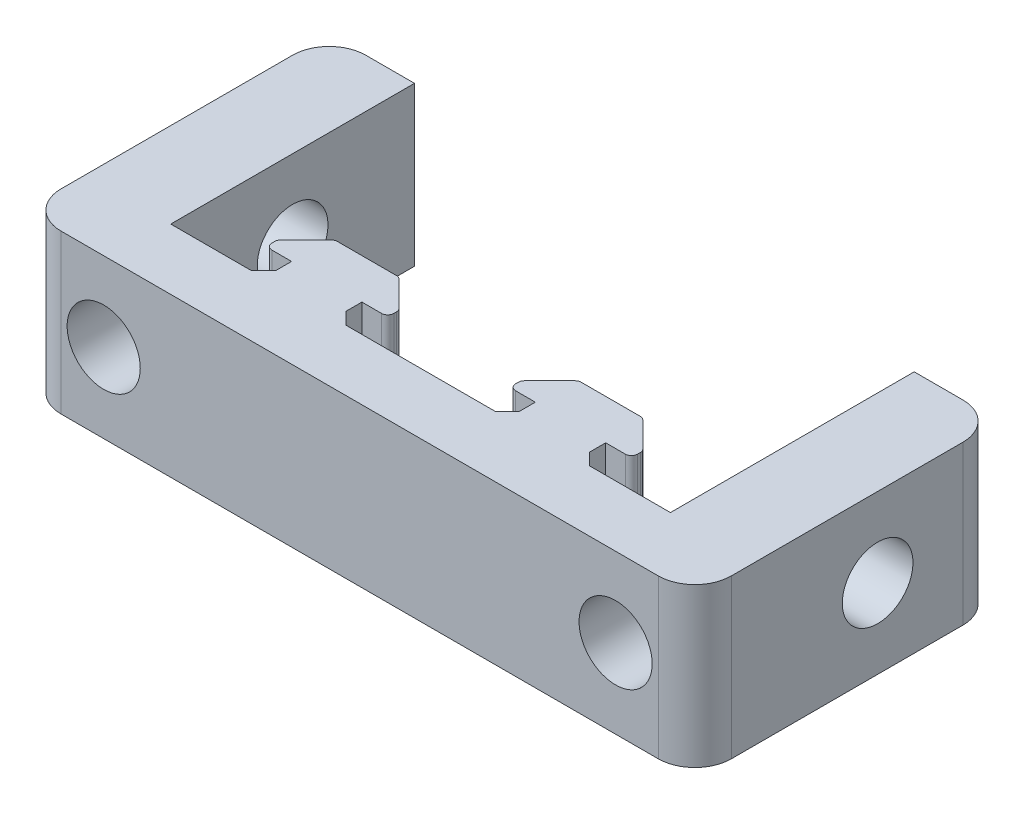
SolidWorks part; units mm, degrees
ref_plane "Front Plane" through (0, 0, 0) normal (0, 0, 1) x (1, 0, 0)
ref_plane "Top Plane" through (0, 0, 0) normal (0, 1, 0) x (1, 0, 0)
ref_plane "Right Plane" through (0, 0, 0) normal (1, 0, 0) x (0, 0, -1)
sketch "Sketch1" plane through (0, 0, 0) normal (0, 0, 1) x (1, 0, 0)
  line L5 (-27.5, -6.5) -> (27.5, -6.5)
  line L6 (-27.5, -6.5) -> (-27.5, 6.5)
  line L7 (-27.5, 6.5) -> (27.5, 6.5)
  line L8 (27.5, -6.5) -> (27.5, 6.5)
  line L9 (-27.5, -6.5) -> (27.5, 6.5) construction
  line L10 (-27.5, 6.5) -> (27.5, -6.5) construction
  point P0 (0, 0)
  dimension "D1" = 13
  dimension "D2" = 55
extrude "Boss-Extrude1" add sketch "Sketch1" along normal blind 10
sketch "Sketch2" plane through (0, 0, 10) normal (0, 0, 1) x (1, 0, 0)
  line L0 (27.5, -6.5) -> (27.5, 6.5) construction
  line L1 (-27.5, -6.5) -> (27.5, -6.5)
  line L2 (-27.5, -6.5) -> (-27.5, 6.5)
  line L3 (-27.5, 6.5) -> (27.5, 6.5)
  line L4 (27.5, -6.5) -> (27.5, 6.5)
  line L5 (-27.5, -6.5) -> (27.5, 6.5) construction
  line L6 (-27.5, 6.5) -> (27.5, -6.5) construction
  line L7 (-27.5, -6.5) -> (27.5, -6.5) construction
  point P0 (0, 0)
extrude "Cut-Extrude1" cut sketch "Sketch2" against normal offset from surface (5 mm away) 5 contours L3 L4 L1 L2 up to face at (0, 0, 0)
sketch "Sketch4" plane through (0, 0, 5) normal (0, 0, 1) x (1, 0, 0)
  line L0 (21, 0) -> (-21, 0) construction
  circle A0 centre (21, 0) radius 3
  circle A1 centre (-21, 0) radius 3
  point P4 (0, 0)
  dimension "D2" = 6
  dimension "D1" = 42
extrude "Cut-Extrude2" cut sketch "Sketch4" against normal up to next
sketch "Sketch5" plane through (0, 6.5, 0) normal (0, 1, 0) x (1, 0, 0)
  line L1 (9.9, 5.5995) -> (12.6324, 5.5995)
  line L2 (12.6324, 5.5995) -> (15, 3.2319)
  line L3 (15, 3.2319) -> (15, 2.3)
  line L4 (15, 2.3) -> (12.8865, 2.3)
  line L5 (12.8865, 2.3) -> (12.8865, 0.9829)
  line L6 (12.8865, 0.9829) -> (13.8694, 0)
  line L7 (6.1306, 0) -> (7.1135, 0.9829)
  line L8 (7.1135, 0.9829) -> (7.1135, 2.3)
  line L9 (7.1135, 2.3) -> (5, 2.3)
  line L10 (5, 2.3) -> (5, 3.2319)
  line L11 (5, 3.2319) -> (7.3676, 5.5995)
  line L12 (7.3676, 5.5995) -> (9.9, 5.5995)
  line L14 (10.1, 5.5995) -> (12.6324, 5.5995) construction
  line L17 (13.8694, 0) -> (6.1306, 0)
  line L18 (12.8865, 0.9829) -> (14.0205, -0.1511) construction
  line L19 (5.9795, -0.1511) -> (7.1135, 0.9829) construction
  line L313 (0, 1.8) -> (0, 0)
  line L314 (0, 0) -> (5.1372, 0)
  line L315 (5.6259, 0.2024) -> (6.6135, 1.19)
  line L316 (6.6135, 1.19) -> (6.6135, 1.8)
  line L317 (6.6135, 1.8) -> (4.5, 1.8)
  line L318 (4.5, 1.8) -> (4.5, 3.439)
  line L319 (4.5, 3.439) -> (7.1605, 6.0995)
  line L320 (7.1605, 6.0995) -> (9.9, 6.0995)
  line L321 (9.9, 6.0995) -> (10, 6.1995)
  line L322 (10, 6.1995) -> (10.1, 6.0995)
  line L323 (10.1, 6.0995) -> (12.8395, 6.0995)
  line L324 (12.8395, 6.0995) -> (15.5, 3.439)
  line L325 (15.5, 3.439) -> (15.5, 1.8)
  line L326 (15.5, 1.8) -> (13.3865, 1.8)
  line L327 (13.3865, 1.8) -> (13.3865, 1.19)
  line L328 (13.3865, 1.19) -> (14.3741, 0.2024)
  line L329 (14.8628, 0) -> (18.5, 0)
  line L330 (20, 1.5) -> (20, 5.1372)
  line L331 (19.7976, 5.6259) -> (18.81, 6.6135)
  line L332 (18.81, 6.6135) -> (18.2, 6.6135)
  line L333 (18.2, 6.6135) -> (18.2, 4.5)
  line L334 (18.2, 4.5) -> (16.561, 4.5)
  line L335 (16.561, 4.5) -> (13.9005, 7.1605)
  line L336 (13.9005, 7.1605) -> (13.9005, 9.9)
  line L337 (13.9005, 9.9) -> (13.8005, 10)
  line L338 (13.8005, 10) -> (13.9005, 10.1)
  line L339 (13.9005, 10.1) -> (13.9005, 12.8395)
  line L340 (13.9005, 12.8395) -> (16.561, 15.5)
  line L341 (16.561, 15.5) -> (18.2, 15.5)
  line L342 (18.2, 15.5) -> (18.2, 13.3865)
  line L343 (18.2, 13.3865) -> (18.81, 13.3865)
  line L344 (18.81, 13.3865) -> (19.7976, 14.3741)
  line L345 (20, 14.8628) -> (20, 18.5)
  line L346 (18.5, 20) -> (14.8628, 20)
  line L347 (14.3741, 19.7976) -> (13.3865, 18.81)
  line L348 (13.3865, 18.81) -> (13.3865, 18.2)
  line L349 (13.3865, 18.2) -> (15.5, 18.2)
  line L350 (15.5, 18.2) -> (15.5, 16.561)
  line L351 (15.5, 16.561) -> (12.8395, 13.9005)
  line L352 (12.8395, 13.9005) -> (10.1, 13.9005)
  line L353 (10.1, 13.9005) -> (10, 13.8005)
  line L354 (10, 13.8005) -> (9.9, 13.9005)
  line L355 (9.9, 13.9005) -> (7.1605, 13.9005)
  line L356 (7.1605, 13.9005) -> (4.5, 16.561)
  line L357 (4.5, 16.561) -> (4.5, 18.2)
  line L358 (4.5, 18.2) -> (6.6135, 18.2)
  line L359 (6.6135, 18.2) -> (6.6135, 18.81)
  line L360 (6.6135, 18.81) -> (5.6259, 19.7976)
  line L361 (5.1372, 20) -> (0, 20)
  line L362 (0, 20) -> (0, 18.2)
  line L363 (0, 18.2) -> (2.7, 18.2)
  line L364 (2.7, 18.2) -> (2.7, 16.239)
  line L365 (2.7, 16.239) -> (6.0995, 12.8395)
  line L366 (6.0995, 12.8395) -> (6.0995, 10.1)
  line L367 (6.0995, 10.1) -> (6.1995, 10)
  line L368 (6.1995, 10) -> (6.0995, 9.9)
  line L369 (6.0995, 9.9) -> (6.0995, 7.1605)
  line L370 (6.0995, 7.1605) -> (2.7, 3.761)
  line L371 (2.7, 3.761) -> (2.7, 1.8)
  line L372 (2.7, 1.8) -> (0, 1.8)
  line L373 (0, 1.8) -> (0, 0) construction
  line L374 (0, 0) -> (5.1372, 0) construction
  line L375 (5.6259, 0.2024) -> (6.6135, 1.19) construction
  line L376 (6.6135, 1.19) -> (6.6135, 1.8) construction
  line L377 (6.6135, 1.8) -> (4.5, 1.8) construction
  line L378 (4.5, 1.8) -> (4.5, 3.439) construction
  line L379 (4.5, 3.439) -> (7.1605, 6.0995) construction
  line L380 (7.1605, 6.0995) -> (9.9, 6.0995) construction
  line L381 (9.9, 6.0995) -> (10, 6.1995) construction
  line L382 (10, 6.1995) -> (10.1, 6.0995) construction
  line L383 (10.1, 6.0995) -> (12.8395, 6.0995) construction
  line L384 (12.8395, 6.0995) -> (15.5, 3.439) construction
  line L385 (15.5, 3.439) -> (15.5, 1.8) construction
  line L386 (15.5, 1.8) -> (13.3865, 1.8) construction
  line L387 (13.3865, 1.8) -> (13.3865, 1.19) construction
  line L388 (13.3865, 1.19) -> (14.3741, 0.2024) construction
  line L389 (14.8628, 0) -> (18.5, 0) construction
  line L390 (20, 1.5) -> (20, 5.1372) construction
  line L391 (19.7976, 5.6259) -> (18.81, 6.6135) construction
  line L392 (18.81, 6.6135) -> (18.2, 6.6135) construction
  line L393 (18.2, 6.6135) -> (18.2, 4.5) construction
  line L394 (18.2, 4.5) -> (16.561, 4.5) construction
  line L395 (16.561, 4.5) -> (13.9005, 7.1605) construction
  line L396 (13.9005, 7.1605) -> (13.9005, 9.9) construction
  line L397 (13.9005, 9.9) -> (13.8005, 10) construction
  line L398 (13.8005, 10) -> (13.9005, 10.1) construction
  line L399 (13.9005, 10.1) -> (13.9005, 12.8395) construction
  line L400 (13.9005, 12.8395) -> (16.561, 15.5) construction
  line L401 (16.561, 15.5) -> (18.2, 15.5) construction
  line L402 (18.2, 15.5) -> (18.2, 13.3865) construction
  line L403 (18.2, 13.3865) -> (18.81, 13.3865) construction
  line L404 (18.81, 13.3865) -> (19.7976, 14.3741) construction
  line L405 (20, 14.8628) -> (20, 18.5) construction
  line L406 (18.5, 20) -> (14.8628, 20) construction
  line L407 (14.3741, 19.7976) -> (13.3865, 18.81) construction
  line L408 (13.3865, 18.81) -> (13.3865, 18.2) construction
  line L409 (13.3865, 18.2) -> (15.5, 18.2) construction
  line L410 (15.5, 18.2) -> (15.5, 16.561) construction
  line L411 (15.5, 16.561) -> (12.8395, 13.9005) construction
  line L412 (12.8395, 13.9005) -> (10.1, 13.9005) construction
  line L413 (10.1, 13.9005) -> (10, 13.8005) construction
  line L414 (10, 13.8005) -> (9.9, 13.9005) construction
  line L415 (9.9, 13.9005) -> (7.1605, 13.9005) construction
  line L416 (7.1605, 13.9005) -> (4.5, 16.561) construction
  line L417 (4.5, 16.561) -> (4.5, 18.2) construction
  line L418 (4.5, 18.2) -> (6.6135, 18.2) construction
  line L419 (6.6135, 18.2) -> (6.6135, 18.81) construction
  line L420 (6.6135, 18.81) -> (5.6259, 19.7976) construction
  line L421 (5.1372, 20) -> (0, 20) construction
  line L422 (0, 20) -> (0, 18.2) construction
  line L423 (0, 18.2) -> (2.7, 18.2) construction
  line L424 (2.7, 18.2) -> (2.7, 16.239) construction
  line L425 (2.7, 16.239) -> (6.0995, 12.8395) construction
  line L426 (6.0995, 12.8395) -> (6.0995, 10.1) construction
  line L427 (6.0995, 10.1) -> (6.1995, 10) construction
  line L428 (6.1995, 10) -> (6.0995, 9.9) construction
  line L429 (6.0995, 9.9) -> (6.0995, 7.1605) construction
  line L430 (6.0995, 7.1605) -> (2.7, 3.761) construction
  line L431 (2.7, 3.761) -> (2.7, 1.8) construction
  line L432 (2.7, 1.8) -> (0, 1.8) construction
  arc A45 (5.1372, 0) -> (5.6259, 0.2024) centre (5.1372, 0.6912) ccw
  arc A46 (14.3741, 0.2024) -> (14.8628, 0) centre (14.8628, 0.6912) ccw
  arc A47 (18.5, 0) -> (20, 1.5) centre (18.5, 1.5) ccw
  arc A48 (20, 5.1372) -> (19.7976, 5.6259) centre (19.3088, 5.1372) ccw
  arc A49 (19.7976, 14.3741) -> (20, 14.8628) centre (19.3088, 14.8628) ccw
  arc A50 (20, 18.5) -> (18.5, 20) centre (18.5, 18.5) ccw
  arc A51 (14.8628, 20) -> (14.3741, 19.7976) centre (14.8628, 19.3088) ccw
  arc A52 (5.6259, 19.7976) -> (5.1372, 20) centre (5.1372, 19.3088) ccw
  arc A53 (5.1372, 0) -> (5.6259, 0.2024) centre (5.1372, 0.6912) ccw construction
  arc A54 (14.3741, 0.2024) -> (14.8628, 0) centre (14.8628, 0.6912) ccw construction
  arc A55 (18.5, 0) -> (20, 1.5) centre (18.5, 1.5) ccw construction
  arc A56 (20, 5.1372) -> (19.7976, 5.6259) centre (19.3088, 5.1372) ccw construction
  arc A57 (19.7976, 14.3741) -> (20, 14.8628) centre (19.3088, 14.8628) ccw construction
  arc A58 (20, 18.5) -> (18.5, 20) centre (18.5, 18.5) ccw construction
  arc A59 (14.8628, 20) -> (14.3741, 19.7976) centre (14.8628, 19.3088) ccw construction
  arc A60 (5.6259, 19.7976) -> (5.1372, 20) centre (5.1372, 19.3088) ccw construction
  arc A61 (5.1372, -0.5) -> (5.9795, -0.1511) centre (5.1372, 0.6912) ccw construction
  arc A62 (14.0205, -0.1511) -> (14.8628, -0.5) centre (14.8628, 0.6912) ccw construction
  dimension "D1" = 0
  dimension "D2" = 0.5
extrude "Boss-Extrude3" add sketch "Sketch5" against normal up to surface (13 mm away) up to face at (0, -6.5, 2.5)
mirror "Mirror1" about plane through (0, 0, 0) normal (1, 0, 0) of "Boss-Extrude3"
sketch "Sketch6" plane through (0, 0, 0) normal (0, 0, -1) x (-1, 0, 0)
  line L0 (13.8694, 6.5) -> (27.5, 6.5) construction
  line L1 (27.5, -6.5) -> (20.5, -6.5)
  line L2 (27.5, -6.5) -> (27.5, 6.5)
  line L3 (27.5, 6.5) -> (20.5, 6.5)
  line L4 (20.5, -6.5) -> (20.5, 6.5)
  line L5 (-27.5, 6.5) -> (-13.8694, 6.5) construction
  line L6 (-27.5, -6.5) -> (-20.5, -6.5)
  line L7 (-27.5, -6.5) -> (-27.5, 6.5)
  line L8 (-27.5, 6.5) -> (-20.5, 6.5)
  line L9 (-20.5, -6.5) -> (-20.5, 6.5)
  dimension "D1" = 41
extrude "Boss-Extrude4" add sketch "Sketch6" along normal blind 20
sketch "Sketch7" plane through (-27.5, 0, 0) normal (-1, 0, 0) x (0, 0, 1)
  line L0 (-20, 0) -> (-10, 0) construction
  line L1 (-20, -6.5) -> (-20, 6.5) construction
  dimension "D1" = 10
hole_wizard "M5 Clearance Hole1" positions "3DSketch1" profile "Sketch8" hole size "M5" standard "ANSI Metric" end condition through all
sketch3d "3DSketch1"
  point P0 (-27.5, 0, -10)
sketch "Sketch8" plane through (-27.5, 0, -10) normal (0, 1, 0) x (0, 0, 1)
  line L0 (0, 0) -> (0, 55)
  line L1 (0, 55) -> (2.9, 55)
  line L2 (2.9, 55) -> (2.9, 0)
  line L5 (2.9, 0) -> (0, 0)
  line L11 (0, -6.35) -> (0, 107.95) construction
  dimension "Thru Hole Dia." = 5.8
  dimension "Thru Hole Depth" = 55
fillet "Fillet1" radius 3 4 edges at (-27.5, 0, 5) (27.5, 0, 5) (-27.5, 0, -20) (27.5, 0, -20)
fillet "Fillet2" radius 0.5 12 edges at (5, 0, -2.3) (15, 0, -2.3) (5, 0, -3.2319) (15, 0, -3.2319) (12.6324, 0, -5.5995) (7.3676, 0, -5.5995) (-12.6324, 0, -5.5995) (-7.3676, 0, -5.5995) (-5, 0, -3.2319) (-5, 0, -2.3) (-15, 0, -3.2319) (-15, 0, -2.3)
